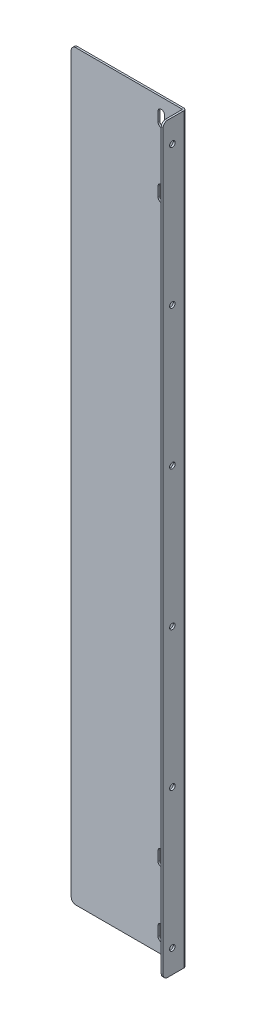
SolidWorks part; units mm, degrees
note: The reader was unsure of these and kept them because the rebuilt part matched: flange length of "边线-法兰1".
ref_plane "前视基准面" through (0, 0, 0) normal (0, 0, 1) x (1, 0, 0)
ref_plane "上视基准面" through (0, 0, 0) normal (0, 1, 0) x (1, 0, 0)
ref_plane "右视基准面" through (0, 0, 0) normal (1, 0, 0) x (0, 0, -1)
sketch "草图1" plane through (0, 0, 0) normal (0, 0, 1) x (1, 0, 0)
  line L1 (122.5, -400) -> (-122.5, -400)
  line L2 (122.5, -400) -> (122.5, 400)
  line L3 (122.5, 400) -> (-122.5, 400)
  line L4 (-122.5, -400) -> (-122.5, 400)
  line L5 (122.5, -400) -> (-122.5, 400) construction
  line L6 (122.5, 400) -> (-122.5, -400) construction
  point P0 (0, 0)
  dimension "D1" = 245
  dimension "D2" = 800
base flange "基体-法兰1" sketch "草图1" thickness 2 reverse thickness direction no parameters "D1"=0.7366
fillet "圆角1" radius 5 4 edges at (122.5, 400, -1) (-122.5, 400, -1) (122.5, -400, -1) (-122.5, -400, -1)
sketch "草图2" plane through (0, 0, 0) normal (0, 0, 1) x (1, 0, 0)
  line L1 (0.5, -427.0069) -> (-0.5, -427.0069)
  line L2 (0.5, -427.0069) -> (0.5, 427.0069)
  line L3 (0.5, 427.0069) -> (-0.5, 427.0069)
  line L4 (-0.5, -427.0069) -> (-0.5, 427.0069)
  line L5 (0.5, -427.0069) -> (-0.5, 427.0069) construction
  line L6 (0.5, 427.0069) -> (-0.5, -427.0069) construction
  point P0 (0, 0)
  dimension "D1" = 1
extrude "切除-拉伸1" cut sketch "草图2" against normal blind 10 normal cut yes
sketch "草图3" plane through (0, 0, 0) normal (0, 0, 1) x (1, 0, 0)
  line L1 (0.5, 400) -> (130.5, 400)
  line L2 (0.5, 400) -> (0.5, -400.3202)
  line L3 (0.5, -400.3202) -> (130.5, -400.3202)
  line L4 (130.5, 400) -> (130.5, -400.3202)
  dimension "D1" = 130
extrude "切除-拉伸2" cut sketch "草图3" against normal blind 10
edge flange "边线-法兰1" sketch "草图8" flange angle 90 flange length 25 flange position material inside bend radius 0.7366 thickness 2 relief rectangular parameters "D6"=10
sketch "草图8" plane through (-0.5, 0, 0) normal (1, 0, 0) x (0, 1, 0)
  line L0 (400, 0) -> (-400, 0) construction
  line L1 (400, 0) -> (-400, 0)
  line L2 (-400, 0) -> (-400, 23)
  line L3 (-400, 23) -> (400, 23)
  line L4 (400, 23) -> (400, 0)
bend "边线折弯1" bend radius 0.7366 bend angle 90 parameters "D5"=1
fillet "圆角2" radius 5 2 edges at (-1.5, 400, 23) (-1.5, -400, 23)
sketch "草图9" plane through (0, 0, 0) normal (0, 0, 1) x (1, 0, 0)
  line L0 (-25.5, 315) -> (-25.5, 305) construction
  line L3 (-25.5, 385) -> (-25.5, 375) construction
  line L4 (-22, 385) -> (-22, 375)
  line L5 (-29, 385) -> (-29, 375)
  line L6 (-22, 315) -> (-22, 305)
  line L9 (-25.5, -385) -> (-25.5, -375) construction
  line L12 (-29, 315) -> (-29, 305)
  line L13 (-0.5, 395) -> (-0.5, -395) construction
  line L14 (-29, -385) -> (-29, -375)
  line L15 (-22, -385) -> (-22, -375)
  line L16 (-25.5, -305) -> (-25.5, -315) construction
  line L17 (-22, -305) -> (-22, -315)
  line L18 (-29, -305) -> (-29, -315)
  arc A2 (-22, 385) -> (-29, 385) centre (-25.5, 385) ccw
  arc A3 (-29, 375) -> (-22, 375) centre (-25.5, 375) ccw
  arc A8 (-29, -385) -> (-22, -385) centre (-25.5, -385) ccw
  arc A9 (-22, -375) -> (-29, -375) centre (-25.5, -375) ccw
  arc A10 (-22, 315) -> (-29, 315) centre (-25.5, 315) ccw
  arc A11 (-29, 305) -> (-22, 305) centre (-25.5, 305) ccw
  arc A12 (-22, -305) -> (-29, -305) centre (-25.5, -305) ccw
  arc A13 (-29, -315) -> (-22, -315) centre (-25.5, -315) ccw
  point P2 (-25.5, -380)
  point P8 (-25.5, 380)
  point P18 (-25.5, 310)
  point P24 (-25.5, -310)
  dimension "D12" = 70
  dimension "D2" = 7
  dimension "D3" = 10
  dimension "D4" = 7
  dimension "D5" = 10
  dimension "D6" = 25
  dimension "D7" = 25
  dimension "D8" = 760
  dimension "D9" = 7
  dimension "D10" = 380
  dimension "D11" = 10
  dimension "D13" = 7
  dimension "D14" = 10
  dimension "D15" = 70
extrude "切除-拉伸3" cut sketch "草图9" against normal blind 10 normal cut yes
hole_wizard "Ø6.0 (6) 直径孔1" positions "草图10" profile "草图11" hole size "Ø6.0" standard "GB" end condition through all
sketch "草图10" plane through (-2.5, 0, 0) normal (-1, 0, 0) x (0, 0, 1)
  line L0 (0.7366, 400) -> (18, 400) construction
  line L1 (23, 395) -> (23, -395) construction
  point P0 (13, 375)
  dimension "D1" = 25
  dimension "D2" = 10
sketch "草图11" plane through (-2.5, 375, 13) normal (0, 1, 0) x (0, 0, 1)
  line L0 (0, 0) -> (0, 2)
  line L1 (0, 2) -> (3, 2)
  line L2 (3, 2) -> (3, 0)
  line L5 (3, 0) -> (0, 0)
  line L11 (0, -6.35) -> (0, 107.95) construction
  dimension "通孔孔直径" = 6
  dimension "通孔孔深度" = 2
pattern_linear "阵列(线性)1" count 6 spacing 150 along (0, -1, 0) of "Ø6.0 (6) 直径孔1"
sketch "折弯-线1" [suppressed] plane through (0, 0, 0) normal (0, 1, 0) x (1, 0, 0)
sketch "边界框1" [suppressed] plane through (0, 0, 0) normal (0, 1, 0) x (1, 0, 0)
sheet metal parameters "钣金1" thickness 2 parameters "D1"=0.7366
flat pattern "平板型式1" [suppressed]
sketch "折弯-线2" plane through (0, 0, 0) normal (0, 1, 0) x (1, 0, 0)
sketch3d "边界框2" [suppressed]
  line L0 (122.5, -400, 0) -> (122.5, 400, 0) construction
  line L1 (-122.5, -400, 0) -> (-122.5, 400, 0) construction
  line L2 (122.5, -400, 0) -> (-122.5, -400, 0) construction
  line L3 (122.5, 400, 0) -> (-122.5, 400, 0) construction
sheet metal parameters "钣金3" thickness 2 parameters "D1"=0.7366
flat pattern "平板型式3"
sketch "折弯-线3" plane through (0, 0, 0) normal (0, 1, 0) x (1, 0, 0)
sketch3d "边界框3" [suppressed]
  line L0 (-0.5001, -400, 0) -> (-0.5, 400, 0) construction
  line L1 (-122.5, -400, 0) -> (-122.4999, 400, 0) construction
  line L2 (-0.5001, -400, 0) -> (-122.5, -400, 0) construction
  line L3 (-0.5, 400, 0) -> (-122.4999, 400, 0) construction
sheet metal parameters "钣金4" thickness 2 parameters "D1"=0.7366
flat pattern "平板型式4"
sketch "折弯-线4" plane through (0, 0, 0) normal (0, 1, 0) x (1, 0, 0)
sketch "边界框4" [suppressed] plane through (0, 0, 0) normal (0, 1, 0) x (1, 0, 0)
sheet metal parameters "钣金5" thickness 2 parameters "D1"=0.7366
flat pattern "平板型式3"
sketch "折弯-线3" plane through (0, 0, 0) normal (0, 0, 1) x (1, 0, 0)
  line L0 (-1.8727, -400) -> (-1.8727, 400) construction
  line L1 (-1.8727, -400) -> (-1.8727, 400) construction
sketch3d "边界框3" [suppressed]
  line L0 (21.7546, -400, 0) -> (21.7546, 400, 0) construction
  line L1 (-122.5, -400, 0) -> (-122.4999, 400, 0) construction
  line L2 (21.7546, -400, 0) -> (-122.5, -400, 0) construction
  line L3 (21.7546, 400, 0) -> (-122.4999, 400, 0) construction
bend of the flat pattern "展平-<边线折弯1>1"
sheet metal parameters "钣金6" thickness 2 parameters "D1"=0.7366
flat pattern "平板型式3"
sketch "折弯-线3" plane through (0, 0, 0) normal (0, 0, 1) x (1, 0, 0)
  line L0 (-1.8727, -400) -> (-1.8727, 400) construction
  line L1 (-1.8727, -400) -> (-1.8727, 400) construction
sketch3d "边界框3" [suppressed]
  line L0 (21.7546, -400, 0) -> (21.7546, 400, 0) construction
  line L1 (-122.5, -400, 0) -> (-122.4999, 400, 0) construction
  line L2 (21.7546, -400, 0) -> (-122.5, -400, 0) construction
  line L3 (21.7546, 400, 0) -> (-122.4999, 400, 0) construction
bend of the flat pattern "展平-<边线折弯1>1"
sheet metal parameters "钣金7" thickness 2 parameters "D1"=0.7366
flat pattern "平板型式3"
sketch "折弯-线3" plane through (0, 0, 0) normal (0, 0, 1) x (1, 0, 0)
  line L0 (-1.8727, -400) -> (-1.8727, 400) construction
  line L1 (-1.8727, -400) -> (-1.8727, 400) construction
sketch3d "边界框3" [suppressed]
  line L0 (21.7546, -400, 0) -> (21.7546, 400, 0) construction
  line L1 (-122.5, -400, 0) -> (-122.4999, 400, 0) construction
  line L2 (21.7546, -400, 0) -> (-122.5, -400, 0) construction
  line L3 (21.7546, 400, 0) -> (-122.4999, 400, 0) construction
bend of the flat pattern "展平-<边线折弯1>1"
sheet metal parameters "钣金8" thickness 2 parameters "D1"=0.7366
flat pattern "平板型式3"
sketch "折弯-线3" plane through (0, 0, 0) normal (0, 0, 1) x (1, 0, 0)
  line L0 (-1.8727, -400) -> (-1.8727, 400) construction
  line L1 (-1.8727, -400) -> (-1.8727, 400) construction
sketch3d "边界框3" [suppressed]
  line L0 (21.7546, -400, 0) -> (21.7546, 400, 0) construction
  line L1 (-122.5, -400, 0) -> (-122.4999, 400, 0) construction
  line L2 (21.7546, -400, 0) -> (-122.5, -400, 0) construction
  line L3 (21.7546, 400, 0) -> (-122.4999, 400, 0) construction
bend of the flat pattern "展平-<边线折弯1>1"
